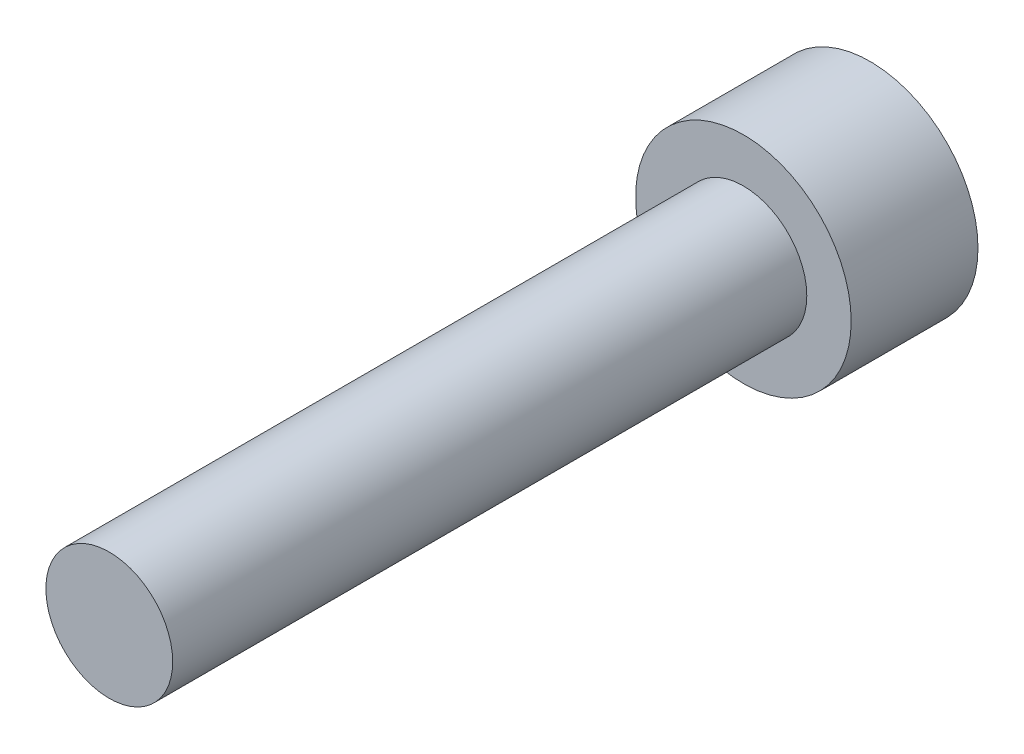
SolidWorks part; units mm, degrees
material "Chrome Stainless Steel"
ref_plane "Front Plane" through (0, 0, 0) normal (0, 0, 1) x (1, 0, 0)
ref_plane "Top Plane" through (0, 0, 0) normal (0, 1, 0) x (1, 0, 0)
ref_plane "Right Plane" through (0, 0, 0) normal (1, 0, 0) x (0, 0, -1)
sketch "Sketch1" plane through (0, 0, 0) normal (0, 0, 1) x (1, 0, 0)
  circle A0 centre (0, 0) radius 4.25
  circle A1 centre (0, 0) radius 2.5
  dimension "D1" = 8.5
  dimension "D2" = 5
extrude "Boss-Extrude3" add sketch "Sketch1" against normal blind 5 contours A0 A1 | A1 region at (-4.1298, 0, 0) region at (0, 0, 0)
extrude "Boss-Extrude4" add sketch "Sketch1<3>" along normal blind 25 contours A1 region at (0, 0, 0)
sketch "Sketch1<3>" plane through (0, 0, 0) normal (0, 0, 1) x (1, 0, 0) same geometry as "Sketch1"
